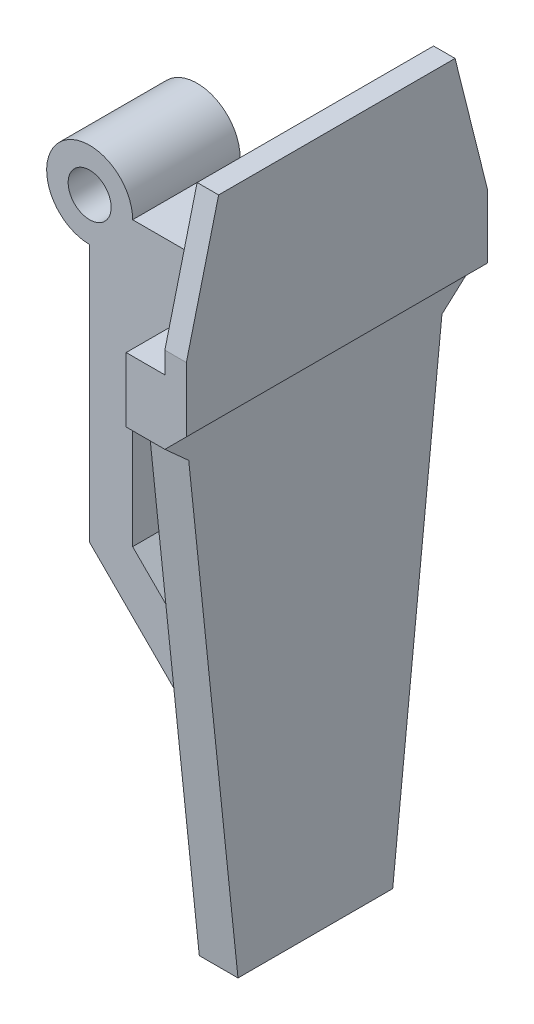
SolidWorks part; units mm, degrees
material "ABS PC"
ref_plane "前视基准面" through (0, 0, 0) normal (0, 0, 1) x (1, 0, 0)
ref_plane "上视基准面" through (0, 0, 0) normal (0, 1, 0) x (1, 0, 0)
ref_plane "右视基准面" through (0, 0, 0) normal (1, 0, 0) x (0, 0, -1)
sketch "草图1" plane through (0, 0, 0) normal (0, 0, 1) x (1, 0, 0)
  line L0 (60.6458, 0.7205) -> (40, 0.7205) construction
  line L1 (54.2884, 0.7205) -> (62.2884, 0.7205)
  line L2 (54.2884, 0.7205) -> (54.2884, -13.2795)
  line L3 (56.2884, -12.451) -> (60.2884, -16.451)
  line L4 (62.2884, 0.7205) -> (62.2884, -13.2795)
  line L5 (54.2884, -13.2795) -> (62.2884, -21.2795)
  line L6 (62.2884, -21.2795) -> (62.2884, -13.2795)
  line L7 (60.2884, -16.451) -> (60.2884, -13.2795)
  line L8 (60.2884, -1.2795) -> (60.2884, -13.2795)
  line L9 (44.3556, 10) -> (44.3556, 0) construction
  line L10 (56.2884, -5.2795) -> (56.2884, -12.451)
  line L11 (60.2884, -1.2795) -> (56.2884, -5.2795)
  line L13 (56.2884, -1.2795) -> (56.2884, -12.451) construction
  line L14 (56.2884, -1.2795) -> (60.2884, -1.2795) construction
  circle A0 centre (54.2884, 0.7205) radius 2
  dimension "D5" = 4
  dimension "D1" = 8
  dimension "D2" = 9.9329
  dimension "D3" = 8
  dimension "D4" = 2
extrude "凸台-拉伸1" add sketch "草图1" along normal blind 2.5 and the other way blind 2.5 contours L1 A0 L2 | L2 L5 L6 L4 L1 | L10 L3 L7 L8 L11 region at (54.0055, 1.0035, 0)
sketch "草图2" plane through (62.2884, 0, 0) normal (1, 0, 0) x (0, 0, -1)
  line L0 (-7, -3.2795) -> (-4.5, -27.2795)
  line L1 (-7, 8.7205) -> (7, 8.7205)
  line L2 (-7, 8.7205) -> (-7, -3.2795)
  line L4 (7, 8.7205) -> (7, -3.2795)
  line L5 (-7, 8.7205) -> (7, -3.2795) construction
  line L6 (-7, -3.2795) -> (7, 8.7205) construction
  line L7 (-4.5, -27.2795) -> (4.5, -27.2795)
  line L8 (4.5, -27.2795) -> (7, -3.2795)
  line L9 (2.5, 0.7205) -> (-2.5, 0.7205) construction
  point P0 (0, 2.7205)
  point P10 (0, 0.7205)
  point P11 (0, -27.2795)
  dimension "D1" = 9
  dimension "D2" = 14
  dimension "D3" = 12
  dimension "D4" = 24
  dimension "D5" = 8
  dimension "D6" = 24
extrude "凸台-拉伸2" add sketch "草图2" along normal blind 3 contours L0 L7 L8 L4 L1 L2
sketch "草图4" plane through (62.2884, 0, 0) normal (-1, 0, 0) x (0, 0, 1)
  line L0 (-7, -0.2795) -> (7, -0.2795)
  line L6 (7, -3.2795) -> (7, 8.7205)
  line L7 (7, 8.7205) -> (-7, 8.7205)
  line L8 (-7, 8.7205) -> (-7, -3.2795)
  line L9 (-7, -3.2795) -> (-4.5, -27.2795)
  line L10 (-4.5, -27.2795) -> (4.5, -27.2795)
  line L11 (4.5, -27.2795) -> (7, -3.2795)
  line L12 (7, -3.2795) -> (7, 8.7205)
  line L13 (7, 8.7205) -> (-7, 8.7205)
  line L14 (-7, 8.7205) -> (-7, -3.2795)
  line L15 (-7, -3.2795) -> (-4.5, -27.2795)
  line L16 (-4.5, -27.2795) -> (4.5, -27.2795)
  line L17 (4.5, -27.2795) -> (7, -3.2795)
  line M7 (2.5, 0.7205) -> (2.5, -21.2795)
  line M8 (2.5, -21.2795) -> (-2.5, -21.2795)
  line M9 (-2.5, -21.2795) -> (-2.5, 0.7205)
  line M11 (7, -3.2795) -> (7, 8.7205)
  line M13 (-7, 8.7205) -> (-7, -3.2795)
  line M14 (-7, -3.2795) -> (-4.5, -27.2795)
  line M15 (-4.5, -27.2795) -> (4.5, -27.2795)
  line M16 (4.5, -27.2795) -> (7, -3.2795)
  dimension "D2" = 3
  dimension "D1" = 0
extrude "凸台-拉伸3" add sketch "草图4" along normal blind 1.8 contours L0 M13 M14 M15 M16 M11 M7 M8 M9 | L0 M9 M8 M7 region at (62.2884, -0.5836, -4.75) region at (62.2884, -10.7795, 0)
sketch "草图5" plane through (0, 0, 0) normal (0, 0, 1) x (1, 0, 0)
  line L0 (62.2884, -27.2795) -> (62.2884, -3.2795)
  line L1 (65.2884, -27.2795) -> (60.4884, -27.2795) construction
  line L3 (62.2884, -3.2795) -> (63.2884, -2.2795)
  line L4 (63.2884, -2.2795) -> (63.2884, 6.7205)
  line L5 (63.2884, 6.7205) -> (62.2884, 6.7205)
  line L6 (62.2884, 8.7205) -> (62.2884, -0.2795) construction
  line L7 (62.2884, 6.7205) -> (62.2884, 8.7205)
  line L8 (62.2884, 8.7205) -> (65.2884, 8.7205)
  line L9 (65.2884, 8.7205) -> (65.2884, -27.2795)
  line L10 (65.2884, -27.2795) -> (62.2884, -27.2795)
  dimension "D1" = 3
  dimension "D2" = 2
  dimension "D3" = 1
  dimension "D4" = 135
  dimension "D5" = 24
extrude "切除-拉伸1" cut sketch "草图5" against normal through all both and the other way through all
sketch "草图6" plane through (62.2884, 0, 0) normal (1, 0, 0) x (0, 0, -1)
  line L4 (-4.5, -27.2795) -> (4.5, -27.2795)
  line L5 (4.5, -27.2795) -> (7, -3.2795)
  line L6 (7, -3.2795) -> (-7, -3.2795)
  line L7 (-7, -3.2795) -> (-4.5, -27.2795)
  line L8 (-4.5, -27.2795) -> (4.5, -27.2795)
  line L9 (4.5, -27.2795) -> (7, -3.2795)
  line L10 (7, -3.2795) -> (-7, -3.2795)
  line L11 (-7, -3.2795) -> (-4.5, -27.2795)
  line L12 (-5.8904, -4.2795) -> (-7, -3.2795)
  line L13 (5.8904, -4.2795) -> (7, -3.2795)
  line L16 (-3.5988, -26.2795) -> (3.5988, -26.2795)
  line L17 (3.5988, -26.2795) -> (5.8904, -4.2795)
  line L18 (5.8904, -4.2795) -> (-5.8904, -4.2795)
  line L19 (-5.8904, -4.2795) -> (-3.5988, -26.2795)
  line L20 (-3.5988, -26.2795) -> (3.5988, -26.2795)
  line L21 (3.5988, -26.2795) -> (5.8904, -4.2795)
  line L22 (5.8904, -4.2795) -> (-5.8904, -4.2795)
  line L23 (-5.8904, -4.2795) -> (-3.5988, -26.2795)
  line M9 (-4.5, -27.2795) -> (4.5, -27.2795)
  line M10 (4.5, -27.2795) -> (7, -3.2795)
  line M12 (-7, -3.2795) -> (-4.5, -27.2795)
  dimension "D1" = 0
  dimension "D2" = 1
extrude "切除-拉伸2" cut sketch "草图6" against normal through all contours L23 L12 L13 L21 L20 M12 M9 M10 region at (62.2884, -15.2507, 5.4736)
sketch "草图7" plane through (63.2884, 0, 0) normal (1, 0, 0) x (0, 0, -1)
  line L0 (-7, 0.7205) -> (-5.5, 6.7205)
  line L1 (-7, 6.7205) -> (-7, -2.2795) construction
  line L2 (7, 6.7205) -> (-7, 6.7205) construction
  line L3 (-5.5, 6.7205) -> (-7, 6.7205)
  line L4 (-7, 6.7205) -> (-7, 0.7205)
  line L5 (5.5, 6.7205) -> (7, 6.7205)
  line L6 (7, 6.7205) -> (7, -2.2795) construction
  line L7 (7, 6.7205) -> (7, 0.7205)
  line L8 (7, 0.7205) -> (5.5, 6.7205)
  dimension "D1" = 1.5
  dimension "D2" = 6
  dimension "D3" = 1.5
  dimension "D4" = 6
extrude "切除-拉伸3" cut sketch "草图7" against normal blind 10
sketch "草图8" plane through (0, 0, 2.5) normal (0, 0, 1) x (1, 0, 0)
  circle A0 centre (54.2884, 0.7205) radius 1
  dimension "D1" = 2
extrude "切除-拉伸4" cut sketch "草图8" against normal through all
